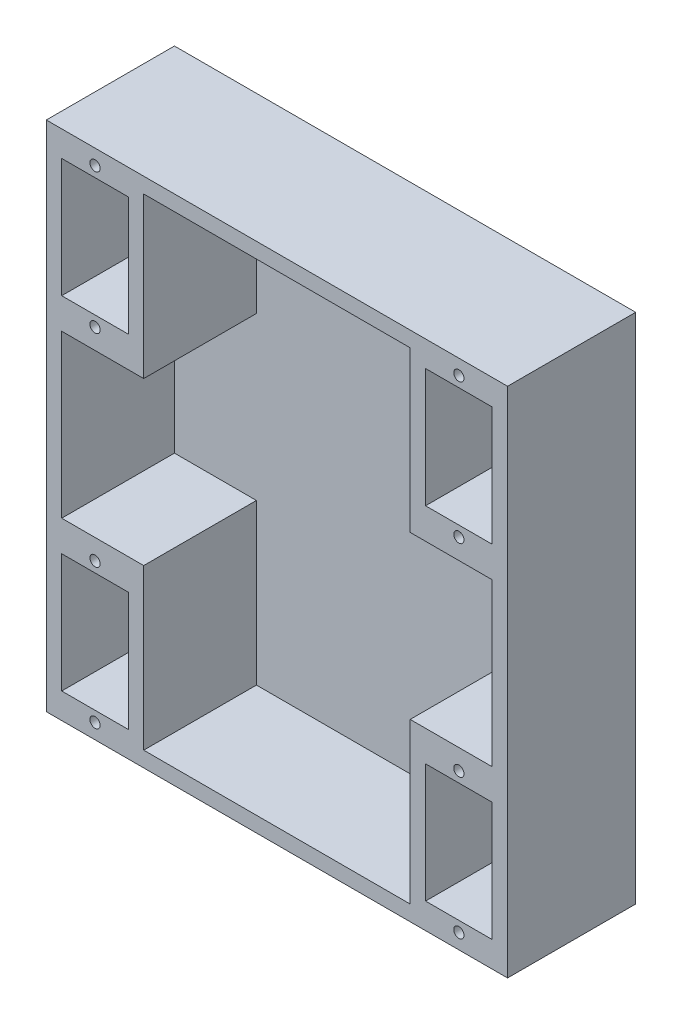
SolidWorks part; units mm, degrees
ref_plane "Plano frontal" through (0, 0, 0) normal (0, 0, 1) x (1, 0, 0)
ref_plane "Plano superior" through (0, 0, 0) normal (0, 1, 0) x (1, 0, 0)
ref_plane "Plano direito" through (0, 0, 0) normal (1, 0, 0) x (0, 0, -1)
sketch "Esboço1" plane through (0, 0, 0) normal (0, 0, 1) x (1, 0, 0)
  line L0 (35.5, 47.05) -> (35.5, 19.75) construction
  line L1 (-45, 50) -> (45, 50)
  line L2 (-45, 50) -> (-45, -50)
  line L3 (-45, -50) -> (45, -50)
  line L4 (45, 50) -> (45, -50)
  line L5 (-45, 50) -> (45, -50) construction
  line L6 (-45, -50) -> (45, 50) construction
  line L7 (29, 45) -> (42, 45)
  line L8 (29, 45) -> (29, 21.8)
  line L9 (29, 21.8) -> (42, 21.8)
  line L10 (42, 45) -> (42, 21.8)
  line L11 (29, 45) -> (42, 21.8) construction
  line L12 (29, 21.8) -> (42, 45) construction
  line L13 (-11.651, 0) -> (14.1427, 0) construction
  line L14 (0, 12.3596) -> (0, -15.2082) construction
  line L15 (29, -21.8) -> (42, -45) construction
  line L16 (29, -45) -> (42, -21.8) construction
  line L17 (35.5, -47.05) -> (35.5, -19.75) construction
  line L18 (42, -45) -> (42, -21.8)
  line L19 (29, -21.8) -> (42, -21.8)
  line L20 (29, -45) -> (29, -21.8)
  line L21 (29, -45) -> (42, -45)
  line L22 (-35.5, -47.05) -> (-35.5, -19.75) construction
  line L23 (-29, -45) -> (-42, -21.8) construction
  line L24 (-29, -21.8) -> (-42, -45) construction
  line L25 (-29, 21.8) -> (-42, 45) construction
  line L26 (-29, 45) -> (-42, 21.8) construction
  line L27 (-35.5, 47.05) -> (-35.5, 19.75) construction
  line L28 (-29, -45) -> (-42, -45)
  line L29 (-29, -45) -> (-29, -21.8)
  line L30 (-29, -21.8) -> (-42, -21.8)
  line L31 (-42, -45) -> (-42, -21.8)
  line L32 (-42, 45) -> (-42, 21.8)
  line L33 (-29, 21.8) -> (-42, 21.8)
  line L34 (-29, 45) -> (-29, 21.8)
  line L35 (-29, 45) -> (-42, 45)
  line L37 (10.2789, -11.1404) -> (10.2789, 35.8596) construction
  line L38 (10.2789, -11.1404) -> (45.2789, -11.1404) construction
  line L39 (45.2789, -11.1404) -> (45.2789, 35.8596) construction
  line L40 (10.2789, 35.8596) -> (45.2789, 35.8596) construction
  line L41 (10.2789, -11.1404) -> (45.2789, 35.8596) construction
  line L42 (45.2789, -11.1404) -> (10.2789, 35.8596) construction
  line L43 (-31.1, -20.1621) -> (31.1, -20.1621) construction
  line L44 (-31.1, -20.1621) -> (-31.1, -42.4621) construction
  line L45 (-31.1, -42.4621) -> (31.1, -42.4621) construction
  line L46 (31.1, -20.1621) -> (31.1, -42.4621) construction
  line L47 (-31.1, -20.1621) -> (31.1, -42.4621) construction
  line L48 (-31.1, -42.4621) -> (31.1, -20.1621) construction
  circle A0 centre (35.5, 19.75) radius 1
  circle A1 centre (35.5, 47.05) radius 1
  circle A2 centre (35.5, 38.5) radius 6.5 construction
  circle A3 centre (35.5, -38.5) radius 6.5 construction
  circle A4 centre (35.5, -47.05) radius 1
  circle A5 centre (35.5, -19.75) radius 1
  circle A6 centre (-35.5, -38.5) radius 6.5 construction
  circle A7 centre (-35.5, 38.5) radius 6.5 construction
  circle A8 centre (-35.5, -19.75) radius 1
  circle A9 centre (-35.5, -47.05) radius 1
  circle A10 centre (-35.5, 47.05) radius 1
  circle A11 centre (-35.5, 19.75) radius 1
  point P0 (0, 0)
  point P6 (35.5, 33.4)
  point P18 (35.5, 33.4)
  point P33 (35.5, -33.4)
  point P54 (-35.5, -33.4)
  point P55 (-35.5, 33.4)
  point P56 (27.7789, 12.3596)
  point P61 (0, -31.3121)
  dimension "D4" = 2
  dimension "D1" = 23.2
  dimension "D2" = 13
  dimension "D3" = 3
  dimension "D5" = 27.3
  dimension "D6" = 5
  dimension "D7" = 47
  dimension "D8" = 35
  dimension "D9" = 62.2
  dimension "D10" = 22.3
  dimension "D11" = 90
  dimension "D12" = 100
extrude "Ressalto-extrusão1" add sketch "Esboço1" along normal blind 25
sketch "Esboço3" plane through (0, 0, 25) normal (0, 0, 1) x (1, 0, 0)
  line L0 (-29, 33.4) -> (-26, 33.4) construction
  line L1 (-26, 47) -> (26, 47)
  line L2 (-26, 47) -> (-26, 15.8)
  line L3 (-26, -47) -> (26, -47)
  line L4 (26, 47) -> (26, 15.8)
  line L5 (-29, 21.8) -> (-29, 45) construction
  line L6 (-26, -15.8) -> (-42, -15.8)
  line L7 (29, 33.4) -> (26, 33.4) construction
  line L8 (29, 45) -> (29, 21.8) construction
  line L9 (0, 50) -> (0, 47) construction
  line L10 (42, -15.8) -> (26, -15.8)
  line L11 (42, -15.8) -> (42, 15.8)
  line L12 (45, 50) -> (-45, 50) construction
  line L13 (0, -50) -> (0, -47) construction
  line L14 (-45, -50) -> (45, -50) construction
  line L15 (42, 15.8) -> (26, 15.8)
  line L16 (-42, -15.8) -> (-42, 15.8)
  line L17 (42, -15.8) -> (-42, 15.8) construction
  line L18 (42, 15.8) -> (-42, -15.8) construction
  line L19 (26, -15.8) -> (26, -47)
  line L20 (-26, -15.8) -> (-26, -47)
  line L21 (-26, 15.8) -> (-42, 15.8)
  line L22 (-45, 50) -> (-45, -50) construction
  line L23 (-29, -21.8) -> (-42, -21.8) construction
  point P8 (0, 0)
  dimension "D1" = 3
  dimension "D2" = 3
  dimension "D3" = 3
  dimension "D4" = 6
extrude "Corte-extrusão1" cut sketch "Esboço3" against normal offset from surface (22 mm away) 3 up to face at (-35.5, -33.4, 0)
sketch "Esboço4" plane through (0, 0, 0) normal (0, 0, -1) x (-1, 0, 0)
  line L0 (-42, -45) -> (-42, -21.8) construction
  line L1 (45, 50) -> (-45, 50)
  line L2 (45, 50) -> (45, -50)
  line L3 (45, -50) -> (-45, -50)
  line L4 (-45, 50) -> (-45, -50)
  line L5 (45, 50) -> (-45, -50) construction
  line L6 (45, -50) -> (-45, 50) construction
  line L7 (-29, -45) -> (-42, -45) construction
  line L9 (-14.847, 0) -> (0, 0) construction
  line L10 (0, -11.1268) -> (0, 0) construction
  circle A0 centre (-35.5, -39.05) radius 1.6
  circle A1 centre (-35.5, 39.05) radius 1.6
  circle A2 centre (35.5, 39.05) radius 1.6
  circle A3 centre (35.5, -39.05) radius 1.6
  point P0 (0, 0)
  point P11 (-42, -33.4)
  point P15 (-35.5, -45)
  dimension "D2" = 3.2
  dimension "D1" = 5.65
extrude "Ressalto-extrusão2" add sketch "Esboço4" against normal blind 2.5
equation "\"D3@Esboço3\"=\"D2@Esboço3\""
